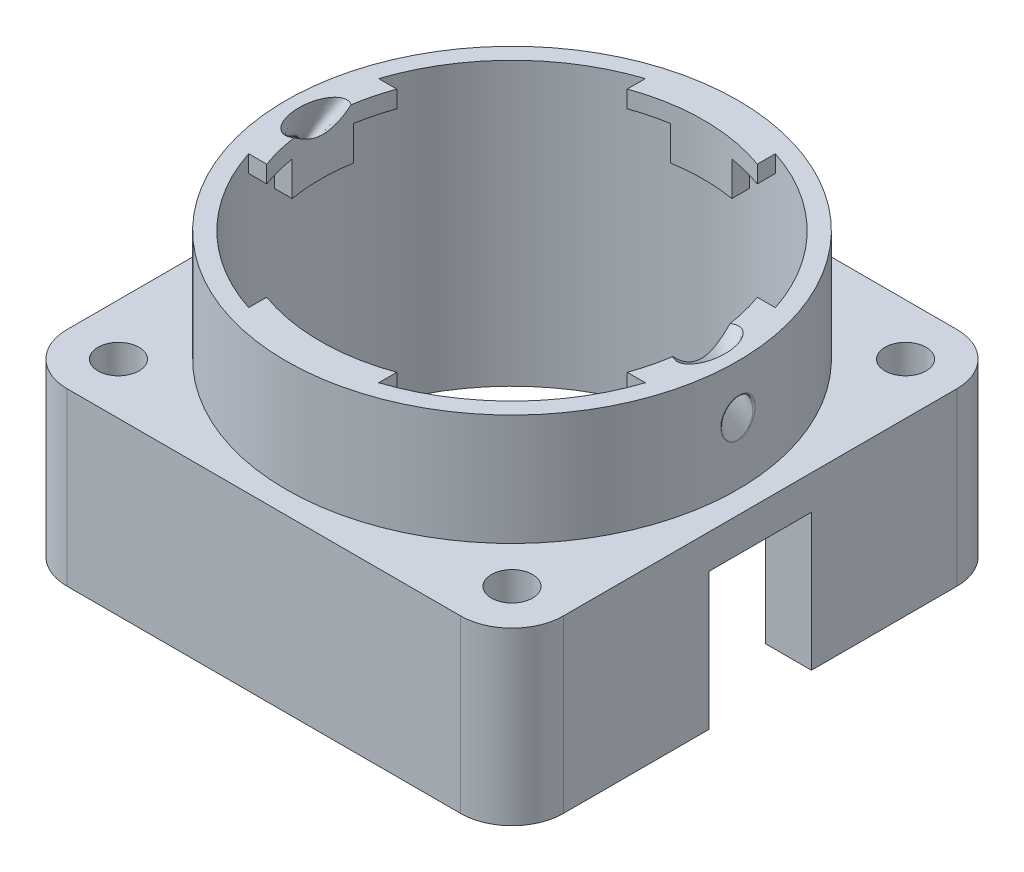
SolidWorks part; units mm, degrees
ref_plane "Front Plane" through (0, 0, 0) normal (0, 0, 1) x (1, 0, 0)
ref_plane "Top Plane" through (0, 0, 0) normal (0, 1, 0) x (1, 0, 0)
ref_plane "Right Plane" through (0, 0, 0) normal (1, 0, 0) x (0, 0, -1)
sketch "Sketch1" plane through (0, 0, 0) normal (0, 1, 0) x (1, 0, 0)
  circle A0 centre (0, 0) radius 12.2
  circle A1 centre (0, 0) radius 13.2
  dimension "D2" = 24.4
  dimension "D1" = 26.4
extrude "Boss-Extrude1" add sketch "Sketch1" against normal blind 2
ref_plane "Plane1" through (0, -2, 0) normal (0, 1, 0) x (1, 0, 0)
sketch "Sketch4" plane through (0, -2, 0) normal (0, 1, 0) x (1, 0, 0)
  circle A0 centre (0, 0) radius 12.2
  circle A1 centre (0, 0) radius 13.2 construction
  circle A2 centre (0, 0) radius 13.2
  dimension "D1" = 24.4
extrude "Boss-Extrude2" add sketch "Sketch4" against normal blind 14.5
sketch "Sketch13" plane through (0, 0, 0) normal (0, 1, 0) x (1, 0, 0)
  line L0 (10.5357, -3.8) -> (11.5931, -3.8)
  line L1 (11.5931, 3.8) -> (10.5357, 3.8)
  line L2 (-3.8, -10.5357) -> (-3.8, -11.5931)
  line L3 (0, 0) -> (0, 12.2) construction
  line L4 (3.8, -11.5931) -> (3.8, -10.5357)
  line L5 (-3.8, 11.5931) -> (-3.8, 10.5357)
  line L7 (3.8, 10.5357) -> (3.8, 11.5931)
  line L8 (-10.5357, 3.8) -> (-11.5931, 3.8)
  line L9 (-11.5931, -3.8) -> (-10.5357, -3.8)
  circle A0 centre (0, 0) radius 12.2 construction
  arc A2 (3.8, 11.5931) -> (-3.8, 11.5931) centre (0, 0) ccw
  arc A3 (-3.8, 10.5357) -> (3.8, 10.5357) centre (0, 0) cw
  arc A4 (10.5357, 3.8) -> (10.5357, -3.8) centre (0, 0) cw
  arc A5 (11.5931, -3.8) -> (11.5931, 3.8) centre (0, 0) ccw
  arc A6 (3.8, -10.5357) -> (-3.8, -10.5357) centre (0, 0) cw
  arc A7 (-3.8, -11.5931) -> (3.8, -11.5931) centre (0, 0) ccw
  arc A8 (-10.5357, -3.8) -> (-10.5357, 3.8) centre (0, 0) cw
  arc A9 (-11.5931, 3.8) -> (-11.5931, -3.8) centre (0, 0) ccw
  point P25 (0, 0)
  dimension "D6" = 7.6
  dimension "D2" = 4
extrude "Boss-Extrude3" add sketch "Sketch13" against normal blind 1
sketch "Sketch19" plane through (0, -1, 0) normal (0, -1, 0) x (1, 0, 0)
  line L0 (-1.8, 12.0665) -> (-1.8, 11.0544)
  line L1 (1.8, 12.0665) -> (1.8, 11.0544)
  line L2 (-3.8, 10.5357) -> (-3.8, 11.5931) construction
  line L3 (3.8, 11.5931) -> (3.8, 10.5357) construction
  line L4 (12.0665, -1.8) -> (11.0544, -1.8)
  line L5 (12.0665, 1.8) -> (11.0544, 1.8)
  line L6 (-1.8, -12.0665) -> (-1.8, -11.0544)
  line L7 (1.8, -12.0665) -> (1.8, -11.0544)
  line L8 (-12.0665, 1.8) -> (-11.0544, 1.8)
  line L9 (-12.0665, -1.8) -> (-11.0544, -1.8)
  arc A0 (-1.8, 12.0665) -> (1.8, 12.0665) centre (0, 0) cw
  arc A1 (3.8, 11.5931) -> (-3.8, 11.5931) centre (0, 0) ccw construction
  circle A2 centre (0, 0) radius 12.2 construction
  arc A3 (-1.8, 11.0544) -> (1.8, 11.0544) centre (0, 0) cw
  arc A4 (3.8, 10.5357) -> (-3.8, 10.5357) centre (0, 0) ccw construction
  arc A5 (11.0544, 1.8) -> (11.0544, -1.8) centre (0, 0) cw
  arc A6 (12.0665, 1.8) -> (12.0665, -1.8) centre (0, 0) cw
  arc A7 (1.8, -11.0544) -> (-1.8, -11.0544) centre (0, 0) cw
  arc A8 (1.8, -12.0665) -> (-1.8, -12.0665) centre (0, 0) cw
  arc A9 (-11.0544, -1.8) -> (-11.0544, 1.8) centre (0, 0) cw
  arc A10 (-12.0665, -1.8) -> (-12.0665, 1.8) centre (0, 0) cw
  point P34 (0, 0)
  dimension "D1" = 2
  dimension "D2" = 2
  dimension "D3" = 4
extrude "Boss-Extrude4" add sketch "Sketch19" along normal blind 2
sketch "Sketch21" plane through (0, 0, 0) normal (0, 0, 1) x (1, 0, 0)
  line L0 (11.45, 0) -> (13.2, -3)
  line L1 (13.2, 0) -> (-13.2, 0) construction
  line L2 (13.2, -16.5) -> (13.2, 0) construction
  dimension "D1" = 0.25
  dimension "D2" = 3
sketch "Sketch22" plane through (0, 0, 0) normal (0, 1, 0) x (1, 0, 0)
  line L1 (0, 0) -> (15.957, 0) construction
  arc A2 (10.5357, -3.8) -> (10.5357, 3.8) centre (0, 0) ccw construction
  ellipse E0 centre (11.45, 0) end of major axis (11.45, -1.8) minor radius 1
  dimension "D1" = 1.8
  dimension "D3" = 11.45
  dimension "D2" = 1
ref_plane "Plane3" through (13.2, 0, 0) normal (1, 0, 0) x (0, 0, -1)
sketch "Sketch23" plane through (13.2, 0, 0) normal (1, 0, 0) x (0, 0, -1)
  circle A0 centre (0, -3) radius 1
  dimension "D1" = 2
  dimension "D2" = 3
loft "Cut-Loft4" cut profiles "Sketch22", "Sketch23" connector at (10.7765, 0, -1.3306) connector at (13.2, -2.1311, -0.4949)
fillet "Fillet2" radius 0.1 1 edges at (13.1947, -3.912, 0.3737)
pattern_circular "CirPattern2" count 2 over 360 about axis through (0, 0, 0) along (0, 1, 0) of "Cut-Loft4", "Fillet2"
ref_plane "Plane4" through (0, -10.5, 0) normal (0, 1, 0) x (1, 0, 0)
sketch "Sketch24" plane through (0, -10.5, 0) normal (0, 1, 0) x (1, 0, 0)
  line L0 (-14.5, 0) -> (14.5, 0) construction
  line L1 (-14.5, 14.5) -> (14.5, 14.5)
  line L2 (-14.5, 14.5) -> (-14.5, -14.5)
  line L3 (-14.5, -14.5) -> (14.5, -14.5)
  line L4 (14.5, 14.5) -> (14.5, -14.5)
  line L5 (0, 14.5) -> (0, 0) construction
  circle A0 centre (0, 0) radius 13.2 construction
  circle A1 centre (0, 0) radius 13.2
  circle A2 centre (-11.5, 11.5) radius 1.2
  circle A3 centre (11.5, 11.5) radius 1.2
  circle A4 centre (11.5, -11.5) radius 1.2
  circle A5 centre (-11.5, -11.5) radius 1.2
  point P10 (0, 0)
  dimension "D3" = 2.4
  dimension "D1" = 29
  dimension "D2" = 29
  dimension "D4" = 11.5
  dimension "D5" = 11.5
extrude "Boss-Extrude5" add sketch "Sketch24" along normal blind 4 and the other way blind 6
fillet "Fillet3" radius 3 4 edges at (14.5, -11.5, -14.5) (14.5, -11.5, 14.5) (-14.5, -11.5, 14.5) (-14.5, -11.5, -14.5)
sketch "Sketch27" plane through (14.5, 0, 0) normal (1, 0, 0) x (0, 0, -1)
  line L0 (-3, -16.5) -> (3, -16.5)
  line L1 (-3, -16.5) -> (-3, -8.5)
  line L2 (-3, -8.5) -> (3, -8.5)
  line L3 (3, -16.5) -> (3, -8.5)
  line L4 (-11.5, -16.5) -> (11.5, -16.5) construction
  line L5 (-11.5, -6.5) -> (11.5, -6.5) construction
  point P6 (0, -16.5)
  point P7 (0, -16.5)
  dimension "D1" = 2
  dimension "D2" = 6
extrude "Cut-Extrude2" cut sketch "Sketch27" against normal blind 10
equation "\"dia_difflayer\"= 13"
equation "\"dia_outer_out\"= 12.5"
equation "\"dia_outer_in\"= 12"
equation "\"dia_inner_out\"= 11"
equation "\"dia_inner_in\"= 10.5"
equation "\"degrees\"= 12.5"
equation "\"d_marker\"= 1"
equation "\"t_marker\"= 0.5"
equation "\"n_markers_1\"= 6"
equation "\"n_markers_2\"= round ( 6 * sin ( 2*\"degrees\" ) / sin ( \"degrees\" ) )"
equation "\"n_markers_3\"= round ( 6 * sin ( 3*\"degrees\" ) / sin ( \"degrees\" ) )"
equation "\"n_markers_4\"= round ( 6 * sin ( 4*\"degrees\" ) / sin ( \"degrees\" ) )"
equation "\"n_markers_5\"= round ( 6 * sin ( 5*\"degrees\" ) / sin ( \"degrees\" ) )"
equation "\"n_teeth\"= 8"
equation "\"tolerance_domes\"= 0.4"
equation "\"tolerance_large\"= 0.4"
equation "\"pinhole_slot\"= 3.8"
equation "\"D6@Sketch13\"=8-\"tolerance_domes\""
equation "\"D2@Sketch1\"=2*\"dia_outer_in\"+\"tolerance_domes\""
equation "\"D1@Sketch1\"=2*\"dia_difflayer\"+\"tolerance_domes\""
equation "\"D1@Sketch4\"=2*\"dia_outer_in\"+\"tolerance_domes\""
